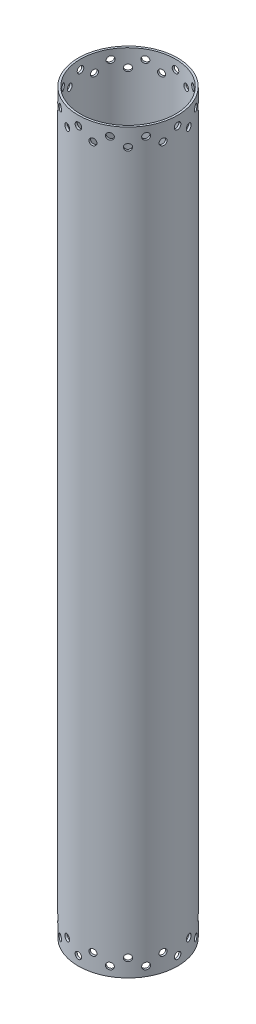
SolidWorks part; units mm, degrees
material "6061-T6 (SS)"
ref_plane "Front Plane" through (0, 0, 0) normal (0, 0, 1) x (1, 0, 0)
ref_plane "Top Plane" through (0, 0, 0) normal (0, 1, 0) x (1, 0, 0)
ref_plane "Right Plane" through (0, 0, 0) normal (1, 0, 0) x (0, 0, -1)
sketch "Sketch2" plane through (0, 0, 0) normal (0, 1, 0) x (1, 0, 0)
  circle A0 centre (0, 0) radius 76.2
  circle A1 centre (0, 0) radius 73.025
  dimension "D1" = 152.4
  dimension "D2" = 3.175
extrude "Boss-Extrude1" add sketch "Sketch2" along normal blind 1130.3
sketch "Sketch3" plane through (0, 0, 0) normal (0, 0, 1) x (1, 0, 0)
  line L0 (0, 1130.3) -> (0, 1116.203) construction
  line L1 (73.025, 1130.3) -> (-73.025, 1130.3) construction
  circle A0 centre (0, 1116.203) radius 5.0419
  dimension "D1" = 10.0838
  dimension "D2" = 14.097
extrude "Cut-Extrude1" cut sketch "Sketch3" against normal blind 1143
ref_plane "Plane1" through (-19.722, 0, 73.6035) normal (-0.2588, 0, 0.9659) x (0, -1, 0)
sketch "Sketch6" plane through (-19.722, 0, 73.6035) normal (-0.2588, 0, 0.9659) x (0, -1, 0)
  line L0 (-1130.3, 0) -> (-1103.503, 0) construction
  line L1 (-1130.3, 76.2) -> (-1130.3, -76.2) construction
  circle A0 centre (-1103.503, 0) radius 5.0419
  dimension "D1" = 10.0838
  dimension "D2" = 26.797
extrude "Cut-Extrude2" cut sketch "Sketch6" against normal blind 25.4
pattern_circular "CirPattern2" count 12 over 360 about axis through (0, 1130.3, 0) along (0, -1, 0) of "Cut-Extrude2", "Cut-Extrude1"
ref_plane "Plane2" through (0, 565.15, 0) normal (0, 1, 0) x (1, 0, 0)
mirror "Mirror1" about plane through (0, 565.15, 0) normal (0, 1, 0) of "CirPattern2"
equation "\"holeDia\"=0.397"
equation "\"D1@Sketch3\"=\"holeDia\""
equation "\"D1@Sketch6\"=\"holeDia\""
equation "\"numHoles\"=12"
equation "\"D1@CirPattern2\"=\"numHoles\""
equation "\"D1@Plane1\"=180/\"numHoles\""
equation "\"D2@Sketch6\"=\"D2@Sketch3\"+0.5"
